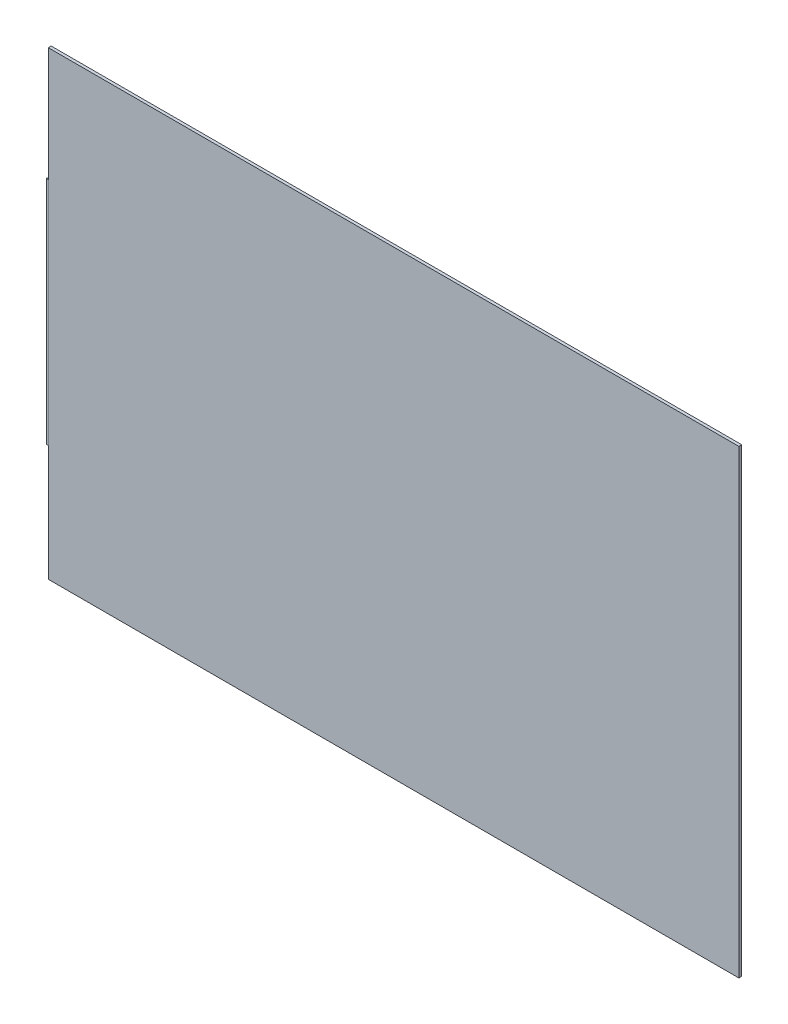
SolidWorks part; units mm, degrees
material "ABS generico"
ref_plane "Piano frontale" through (0, 0, 0) normal (0, 0, 1) x (1, 0, 0)
ref_plane "Piano superiore" through (0, 0, 0) normal (0, 1, 0) x (1, 0, 0)
ref_plane "Piano destro" through (0, 0, 0) normal (1, 0, 0) x (0, 0, -1)
sketch "Schizzo1" plane through (0, 0, 0) normal (0, 0, 1) x (1, 0, 0)
  line L1 (-600, -400) -> (600, -400)
  line L2 (-600, -400) -> (-600, 400)
  line L3 (-600, 400) -> (600, 400)
  line L4 (600, -400) -> (600, 400)
  line L5 (-600, -400) -> (600, 400) construction
  line L6 (-600, 400) -> (600, -400) construction
  point P0 (0, 0)
  dimension "D1" = 800
  dimension "D2" = 1200
extrude "Estrusione-Estrusione1" add sketch "Schizzo1" along normal blind 5
sketch "Schizzo2" plane through (-600, 0, 0) normal (-1, 0, 0) x (0, 0, 1)
  line L0 (2.5, 400) -> (2.5, -400) construction
  line L3 (5, 400) -> (0, 400) construction
  line L8 (5, -400) -> (0, -400) construction
  line L10 (1.5, 200) -> (3.5, 200)
  line L11 (1.5, 200) -> (1.5, -200)
  line L12 (1.5, -200) -> (3.5, -200)
  line L13 (3.5, 200) -> (3.5, -200)
  line L14 (1.5, 200) -> (3.5, -200) construction
  line L15 (1.5, -200) -> (3.5, 200) construction
  point P6 (2.5, 0)
  dimension "D1" = 2
  dimension "D2" = 400
extrude "Estrusione-Estrusione2" add sketch "Schizzo2" along normal blind 5
